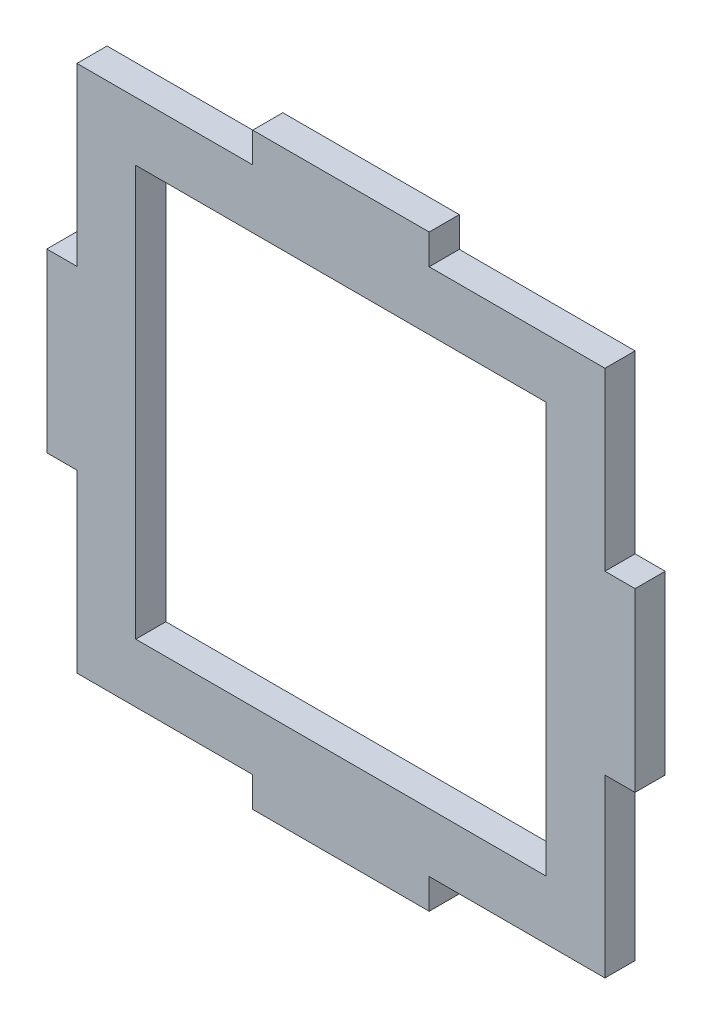
SolidWorks part; units mm, degrees
ref_plane "Front Plane" through (0, 0, 0) normal (0, 0, 1) x (1, 0, 0)
ref_plane "Top Plane" through (0, 0, 0) normal (0, 1, 0) x (1, 0, 0)
ref_plane "Right Plane" through (0, 0, 0) normal (1, 0, 0) x (0, 0, -1)
sketch "Sketch3" plane through (0, 0, 0) normal (0, 0, 1) x (1, 0, 0)
  line L0 (59.88, 89.76) -> (89.76, 89.76)
  line L1 (0, 0) -> (29.88, 0)
  line L2 (0, 0) -> (0, 29.88)
  line L3 (0, 89.76) -> (29.88, 89.76)
  line L4 (89.76, 0) -> (89.76, 29.88)
  line L5 (89.76, 59.88) -> (89.76, 89.76)
  line L6 (29.88, 89.76) -> (29.88, 94.88)
  line L7 (29.88, 94.88) -> (59.88, 94.88)
  line L8 (59.88, 89.76) -> (59.88, 94.88)
  line L9 (89.76, 59.88) -> (94.88, 59.88)
  line L10 (0, 59.88) -> (0, 89.76)
  line L11 (89.76, 29.88) -> (94.88, 29.88)
  line L12 (94.88, 59.88) -> (94.88, 29.88)
  line L14 (59.88, 0) -> (59.88, -5.12)
  line L15 (59.88, -5.12) -> (29.88, -5.12)
  line L16 (29.88, 0) -> (29.88, -5.12)
  line L17 (0, 59.88) -> (-5.12, 59.88)
  line L18 (59.88, 0) -> (89.76, 0)
  line L19 (0, 29.88) -> (-5.12, 29.88)
  line L20 (-5.12, 59.88) -> (-5.12, 29.88)
  dimension "D1" = 5.12
  dimension "D2" = 89.76
  dimension "D3" = 30
extrude "Boss-Extrude2" add sketch "Sketch3" along normal blind 5.12
sketch "Sketch4" plane through (0, 0, 5.12) normal (0, 0, 1) x (1, 0, 0)
  line L0 (14.94, 89.76) -> (14.94, 79.76) construction
  line L1 (10, 10) -> (79.76, 10)
  line L2 (10, 10) -> (10, 79.76)
  line L3 (10, 79.76) -> (79.76, 79.76)
  line L4 (79.76, 10) -> (79.76, 79.76)
  line L5 (29.88, 89.76) -> (0, 89.76) construction
  line L6 (0, 74.82) -> (10, 74.82) construction
  line L7 (0, 89.76) -> (0, 59.88) construction
  line L8 (19.9291, 0) -> (19.9291, 10) construction
  line L9 (0, 0) -> (29.88, 0) construction
  line L10 (79.76, 22.9589) -> (89.76, 22.9589) construction
  line L11 (89.76, 0) -> (89.76, 29.88) construction
  dimension "D1" = 10
extrude "Cut-Extrude1" cut sketch "Sketch4" against normal through all
equation "\"mdf\"=\"mdf@fmv1.assembly\""
equation "\"D1@Sketch3\" = \"mdf\""
equation "\"D2@Sketch3\" = 100-2*\"mdf\""
equation "\"D1@Boss-Extrude2\"=\"mdf\""
equation "\"D1@Sketch4\" = 10"
